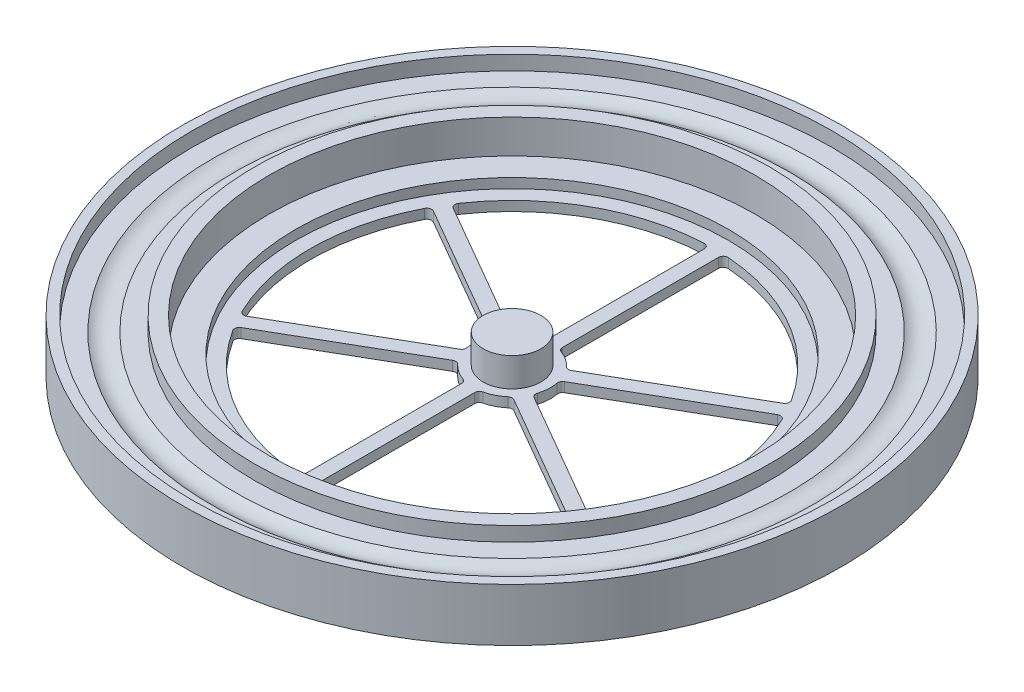
SolidWorks part; units mm, degrees
material "ABS"
ref_plane "Front Plane" through (0, 0, 0) normal (0, 0, 1) x (1, 0, 0)
ref_plane "Top Plane" through (0, 0, 0) normal (0, 1, 0) x (1, 0, 0)
ref_plane "Right Plane" through (0, 0, 0) normal (1, 0, 0) x (0, 0, -1)
sketch "Sketch1" plane through (0, 0, 0) normal (0, 0, 1) x (1, 0, 0)
  line L0 (0, 0) -> (0, 8)
  line L1 (0, 8) -> (6, 8)
  line L2 (6, 8) -> (6, 2)
  line L3 (6, 2) -> (45, 2)
  line L4 (45, 2) -> (45, 4)
  line L5 (45, 4) -> (50.5, 4)
  line L6 (50.5, 4) -> (50.5, 11)
  line L8 (68.5, 11) -> (68.5, 0)
  line L9 (68.5, 0) -> (0, 0)
  line L10 (68.5, 11) -> (66.5, 11)
  line L11 (66.5, 11) -> (66.5, 8)
  line L12 (66.5, 8) -> (62.3516, 8)
  line L13 (50.5, 11) -> (53.5, 11)
  line L14 (53.5, 11) -> (53.5, 8)
  line L15 (53.5, 8) -> (57.6484, 8)
  arc A0 (57.6484, 8) -> (62.3516, 8) centre (60, 11.6) ccw
  point P14 (0, 0)
  dimension "D3" = 4.3
  dimension "D1" = 50.5
  dimension "D2" = 7
  dimension "D4" = 60
  dimension "D5" = 6.5
  dimension "D6" = 6
  dimension "D7" = 2
  dimension "D8" = 8
  dimension "D9" = 2
  dimension "D10" = 2
  dimension "D11" = 45
  dimension "D12" = 6.5
  dimension "D13" = 3
  dimension "D14" = 0.6
revolve "Revolve1" add sketch "Sketch1" angle 360 about L0
sketch "Sketch2" plane through (0, 0, 0) normal (0, 1, 0) x (1, 0, 0)
  line L0 (0, 0) -> (0, 42) construction
  line L1 (0, 0) -> (-36.3731, 21) construction
  line L4 (-34.4119, 22.1771) -> (-6.3485, 5.9747)
  line L5 (-1, 40.9512) -> (-1, 8.775)
  arc A0 (-2.0488, 41.95) -> (-34.739, 23.6052) centre (0, 0) ccw
  arc A1 (-5.1986, 6.0806) -> (-1.7778, 7.8) centre (0, 0) cw
  arc A6 (-1.7778, 7.8) -> (-1, 8.775) centre (-2, 8.775) ccw
  arc A7 (-5.1986, 6.0806) -> (-6.3485, 5.9747) centre (-5.8485, 6.8407) cw
  arc A8 (-1, 40.9512) -> (-2.0488, 41.95) centre (-2, 40.9512) ccw
  arc A9 (-34.4119, 22.1771) -> (-34.739, 23.6052) centre (-33.9119, 23.0431) cw
  point P5 (0, 0)
  point P8 (0, 8)
  point P10 (0, 0)
  point P11 (-6.9282, 4)
  point P13 (0, 0)
  point P14 (0, 0)
  point P15 (0, 0)
  point P16 (0, 0)
  dimension "D2" = 42
  dimension "D3" = 8
  dimension "D4" = 2
  dimension "D5" = 2
  dimension "D6" = 1
  dimension "D1" = 60
extrude "Cut-Extrude1" cut sketch "Sketch2" along normal through all
pattern_circular "CirPattern1" count 6 over 360 about axis through (0, 8, 0) along (0, -1, 0) of "Cut-Extrude1"
